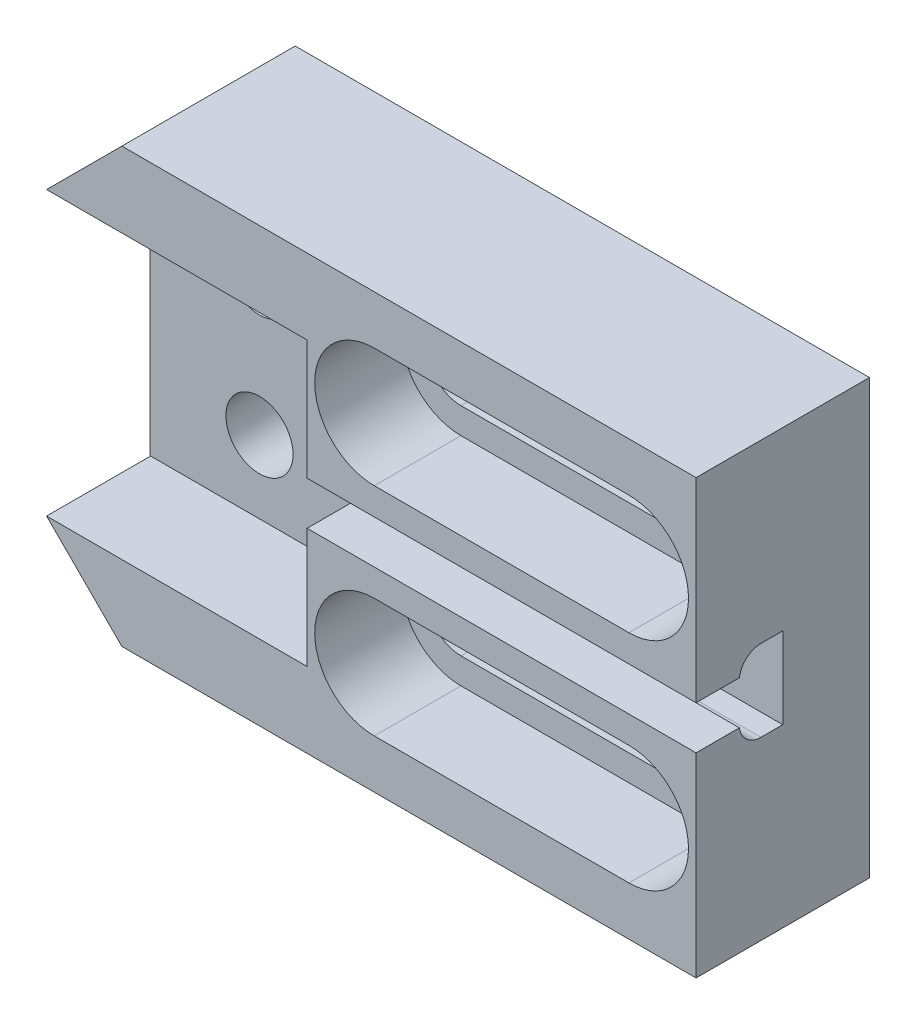
SolidWorks part; units mm, degrees
ref_plane "Front Plane" through (0, 0, 0) normal (0, 0, 1) x (1, 0, 0)
ref_plane "Top Plane" through (0, 0, 0) normal (0, 1, 0) x (1, 0, 0)
ref_plane "Right Plane" through (0, 0, 0) normal (1, 0, 0) x (0, 0, -1)
sketch "ProfileSketch3" plane through (0, 0, 0) normal (0, 0, 1) x (1, 0, 0)
  line L0 (0, 20) -> (30, 20)
  line L1 (0, 0) -> (30, 0)
  line L2 (0, 0) -> (0, 20)
  line L4 (30, 0) -> (30, 20)
  line L9 (15.15, 15) -> (26.9, 15) construction
  line L10 (15.15, 16.55) -> (26.9, 16.55)
  line L11 (15.15, 13.45) -> (26.9, 13.45)
  line L12 (15.15, 5) -> (26.9, 5) construction
  line L13 (15.15, 6.55) -> (26.9, 6.55)
  line L14 (15.15, 3.45) -> (26.9, 3.45)
  arc A4 (15.15, 16.55) -> (15.15, 13.45) centre (15.15, 15) ccw
  arc A5 (26.9, 13.45) -> (26.9, 16.55) centre (26.9, 15) ccw
  arc A6 (15.15, 6.55) -> (15.15, 3.45) centre (15.15, 5) ccw
  arc A7 (26.9, 3.45) -> (26.9, 6.55) centre (26.9, 5) ccw
  point P4 (21.025, 15)
  point P12 (21.025, 5)
  dimension "D4" = 3.1
  dimension "D2" = 3.1
  dimension "D6" = 30
  dimension "D1" = 20
  dimension "D3" = 10
  dimension "D5" = 5
  dimension "D7" = 15.15
extrude "ProfileBoss-Extrude1" add sketch "ProfileSketch3" along normal blind 8
sketch "MicroSwitchCutSketch4" plane through (0, 0, 8) normal (0, 0, 1) x (1, 0, 0)
  line L0 (30, 20) -> (0, 20) construction
  line L1 (0, 16.525) -> (12.05, 16.525)
  line L2 (0, 16.525) -> (0, 3.475)
  line L3 (0, 3.475) -> (12.05, 3.475)
  line L4 (12.05, 16.525) -> (12.05, 3.475)
  dimension "D1" = 12.05
  dimension "D2" = 13.05
  dimension "D3" = 3.475
extrude "MicroSwitchCut-Extrude1" cut sketch "MicroSwitchCutSketch4" against normal blind 4.8
sketch "Sketch5" plane through (0, 0, 3.2) normal (0, 0, 1) x (1, 0, 0)
  line L0 (0, 3.475) -> (12.05, 3.475) construction
  line L2 (12.05, 3.475) -> (12.05, 16.525) construction
  line L4 (12.05, 16.525) -> (0, 16.525) construction
  circle A0 centre (5.05, 13.175) radius 1.55
  circle A1 centre (5.05, 6.825) radius 1.55
  point P10 (11.05, 8.8)
  point P11 (0, 8.8)
  point P12 (15, 21.85)
  point P13 (11.05, 21.85)
  point P14 (15, 0)
  point P15 (15, 21.85)
  point P16 (0, 0)
  point P17 (15, 0)
  point P18 (0, 8.8)
  point P19 (0, 0)
  point P20 (-1, 8.8)
  point P21 (0, 8.8)
  point P22 (-1, 21.85)
  point P23 (-1, 8.8)
  point P24 (15, 21.85)
  point P25 (-1, 21.85)
  point P26 (15, 0)
  point P27 (15, 21.85)
  point P28 (0, 0)
  point P29 (15, 0)
  point P30 (0, 8.8)
  point P31 (0, 0)
  point P32 (11.05, 21.85)
  point P33 (-1, 21.85)
  point P34 (11.05, 8.8)
  point P35 (11.05, 21.85)
  point P36 (-1, 8.8)
  point P37 (0, 8.8)
  point P38 (0, 8.8)
  point P39 (11.05, 8.8)
  point P40 (-1, 21.85)
  point P41 (-1, 8.8)
  point P42 (11.05, 8.8)
  point P43 (11.05, 21.85)
  point P44 (0, 0)
  point P45 (15, 0)
  point P46 (0, 0)
  point P47 (0, 8.8)
  point P48 (-1, 21.85)
  point P49 (15, 21.85)
  point P50 (15, 0)
  point P51 (15, 21.85)
  point P52 (-1, 21.85)
  point P53 (-1, 8.8)
  point P54 (-1, 8.8)
  point P55 (0, 8.8)
  point P56 (-1, 21.85)
  point P57 (-1, 8.8)
  point P58 (-1, 21.85)
  point P59 (11.05, 21.85)
  point P60 (-1, 21.85)
  point P61 (-1, 8.8)
  point P62 (-1, 8.8)
  point P63 (11.05, 8.8)
  point P64 (11.05, 21.85)
  point P65 (11.05, 8.8)
  point P66 (2.75, 0)
  point P67 (-2.75, 0)
  point P68 (0, -2.75)
  point P69 (0, 2.75)
  dimension "D4" = 3.1
  dimension "D3" = 7
  dimension "D2" = 3.35
  dimension "D1" = 3.35
extrude "MicroSwitchMountingHolesCut-Extrude2" cut sketch "Sketch5" against normal blind 3.1
sketch "SmallChannelCableSketch6" plane through (0, 0, 8) normal (0, 0, 1) x (1, 0, 0)
  line L0 (12.05, 3.475) -> (12.05, 16.525) construction
  line L1 (12.05, 11) -> (30, 11)
  line L2 (12.05, 11) -> (12.05, 9)
  line L3 (12.05, 9) -> (30, 9)
  line L4 (30, 11) -> (30, 9)
  line L5 (30, 0) -> (30, 20) construction
  line L6 (0, 3.475) -> (12.05, 3.475) construction
  point P10 (1, 21.85)
  point P11 (1, 13.05)
  point P12 (16, 21.85)
  point P13 (1, 21.85)
  point P14 (16, 0)
  point P15 (16, 21.85)
  point P16 (12.05, 0)
  point P17 (16, 0)
  point P18 (1, 13.05)
  point P19 (0, 13.05)
  point P20 (1, 21.85)
  point P21 (1, 13.05)
  point P22 (16, 21.85)
  point P23 (1, 21.85)
  point P24 (16, 0)
  point P25 (16, 21.85)
  point P26 (0, 0)
  point P27 (16, 0)
  point P28 (0, 13.05)
  point P29 (0, 0)
  point P30 (12.05, 13.05)
  point P31 (1, 13.05)
  point P32 (1, 13.05)
  point P33 (0, 13.05)
  point P34 (12.05, 0)
  point P35 (12.05, 13.05)
  point P36 (0, 0)
  point P37 (12.05, 0)
  point P38 (0, 13.05)
  point P39 (0, 0)
  point P40 (12.05, 13.05)
  point P41 (1, 13.05)
  point P42 (12.05, 0)
  point P43 (12.05, 13.05)
  point P44 (5.05, 9.7)
  point P45 (6.5323, 10.1532)
  point P46 (5.05, 3.35)
  point P47 (6.5323, 3.8032)
  point P48 (5.05, 9.7)
  point P49 (6.5323, 10.1532)
  point P50 (5.05, 3.35)
  point P51 (6.5323, 3.8032)
  point P52 (0, 0)
  point P53 (16, 0)
  point P54 (0, 0)
  point P55 (0, 13.05)
  point P56 (1, 21.85)
  point P57 (16, 21.85)
  point P58 (16, 0)
  point P59 (16, 21.85)
  point P60 (1, 21.85)
  point P61 (1, 13.05)
  point P62 (1, 13.05)
  point P63 (0, 13.05)
  dimension "D2" = 5.525
extrude "SmallChannelCableCut-Extrude3" cut sketch "SmallChannelCableSketch6" against normal blind 2
sketch "LargeChannelCableSketch7" plane through (0, 0, 6) normal (0, 0, 1) x (1, 0, 0)
  line L0 (12.05, 11) -> (12.05, 16.525) construction
  line L1 (12.05, 11.875) -> (30, 11.875)
  line L2 (12.05, 11.875) -> (12.05, 8.125)
  line L3 (12.05, 8.125) -> (30, 8.125)
  line L4 (30, 11.875) -> (30, 8.125)
  line L5 (30, 0) -> (30, 9) construction
  line L6 (30, 11) -> (12.05, 11) construction
  dimension "D1" = 0.875
  dimension "D2" = 3.75
extrude "LargeChannelCableCut-Extrude4" cut sketch "LargeChannelCableSketch7" against normal blind 2
chamfer "Chamfer1" distance 1 angle 45 1 edges at (12.05, 10, 4)
sketch "Sketch6" plane through (0, 0, 8) normal (0, 0, 1) x (1, 0, 0)
  line L0 (15.15, 15) -> (26.9, 15) construction
  line L1 (15.15, 17.75) -> (26.9, 17.75)
  line L2 (15.15, 12.25) -> (26.9, 12.25)
  line L3 (15.15, 5) -> (26.9, 5) construction
  line L4 (15.15, 7.75) -> (26.9, 7.75)
  line L5 (15.15, 2.25) -> (26.9, 2.25)
  arc A0 (15.15, 17.75) -> (15.15, 12.25) centre (15.15, 15) ccw
  arc A1 (26.9, 12.25) -> (26.9, 17.75) centre (26.9, 15) ccw
  arc A2 (15.15, 7.75) -> (15.15, 2.25) centre (15.15, 5) ccw
  arc A3 (26.9, 2.25) -> (26.9, 7.75) centre (26.9, 5) ccw
  point P4 (21.025, 15)
  point P9 (21.025, 5)
  dimension "D1" = 5.5
extrude "MountSLotBoreCut-Extrude1" cut sketch "Sketch6" against normal blind 4
chamfer "Chamfer2" distance 3.5 angle 45 2 edges at (0, 20, 4) (0, 0, 4)
fillet "Fillet3" radius 1 2 edges at (21.025, 11.875, 6) (21.025, 8.125, 6)
equation "\"SK8RodShaftSupportHeight\"= 42mm"
equation "\"SK8RodShaftSupportLength\"= 15mm"
equation "\"SK8MountHoleDiameter\"= 5mm"
equation "\"SK8RiserWidth\"= 6.75mm'Measured to meet Nema17 Mount Hole Center axis"
equation "\"SK8MountHoleFromSide\"= \"SK8RodShaftSupportLength\" / 2"
equation "\"SK8MountHoleFromEitherEnd\"= 5.5mm"
equation "\"MicroSwitchCutOutLength\"= 13.05mm"
equation "\"MicroSwitchHeight\"= 6.55mm"
equation "\"MicroSwitchMountingHoleOffsetFromSide\"= 3.35mm"
equation "\"MicroSwitchTerminalHeight\"= 3.5mm"
equation "\"MicroSwitchExtraMountingHeight\"= 2mm"
equation "\"MicroSwitchDepth\"= 2.8mm"
equation "\"MicroSwitchMountingHoleOffsetFromBottom\"= 7mm"
equation "\"M2HeatInsertHoleDiameter\"= 3mm + .1mm'Add .1mm for printing"
equation "\"M2HeatInsertHoleDepth\"= 3.1mm'Spec"
equation "\"D1@ProfileBoss-Extrude1\" = \"SK8RiserWidth\""
equation "\"D1@MicroSwitchCutSketch4\"=\"MicroSwitchCutOutHeight\""
equation "\"D2@MicroSwitchCutSketch4\" = \"MicroSwitchCutOutLength\""
equation "\"D1@MicroSwitchCut-Extrude1\"=\"MicroSwitchDepth\" + 2mm"
equation "\"D3@Sketch5\"=\"MicroSwitchMountingHoleOffsetFromBottom\""
equation "\"D4@Sketch5\"=\"M2HeatInsertHoleDiameter\""
equation "\"D1@MicroSwitchMountingHolesCut-Extrude2\" = \"M2HeatInsertHoleDepth\""
equation "\"MicroSwitchCutOutHeight\"= \"MicroSwitchExtraMountingHeight\" + \"MicroSwitchTerminalHeight\" + \"MicroSwitchHeight\""
equation "\"EndStopCableWidth\"= 3.75mm"
equation "\"D1@SmallChannelCableSketch6\" = \"EndStopCableDepth\""
equation "\"EndStopCableDepth\"= 2mm"
equation "\"D1@SmallChannelCableCut-Extrude3\"=\"EndStopCableDepth\""
equation "\"D1@LargeChannelCableSketch7\" =  ( \"EndStopCableWidth\" - \"EndStopCableDepth\" )  / 2"
equation "\"D2@LargeChannelCableSketch7\" = \"EndStopCableWidth\""
equation "\"D1@LargeChannelCableCut-Extrude4\" = \"EndStopCableDepth\""
equation "\"D6@ProfileSketch3\"=\"SK8RodShaftSupportLength\"  *2"
equation "\"D2@Sketch5\"=\"MicroSwitchMountingHoleOffsetFromSide\""
equation "\"D1@Sketch6\"= \"SK8MountHoleFromEitherEnd\""
equation "\"D1@ProfileSketch3\"=\"YAxisEndStopMicroSwitchHolderHeight\""
equation "\"Nema17StepperMountSlotDistance\"=31"
equation "\"YAxisEndStopMicroSwitchHolderHeight\"= \"YAxisEndStopHolderDistanceBetweenMountingScrews\" * 2"
equation "\"M3ScrewDiameter\"= 3mm + .1mm'Add .1mm for printing"
equation "\"D3@MicroSwitchCutSketch4\"=(\"YAxisEndStopMicroSwitchHolderHeight\"-\"MicroSwitchCutOutLength\")/2"
equation "\"D2@SmallChannelCableSketch6\"=(\"MicroSwitchCutOutLength\"-\"EndStopCableDepth\")/2"
equation "\"D2@ProfileSketch3\"=\"M3ScrewDiameter\""
equation "\"D4@ProfileSketch3\"=\"M3ScrewDiameter\""
equation "\"D5@ProfileSketch3\"=\"YAxisEndStopHolderDistanceBetweenMountingScrews\"/2"
equation "\"D7@ProfileSketch3\"=\"MicroSwitchCutOutHeight\" + \"M3ScrewDiameter\""
equation "\"YAxisEndStopHolderDistanceBetweenMountingScrews\"= 10mm"
equation "\"D3@ProfileSketch3\"=\"YAxisEndStopHolderDistanceBetweenMountingScrews\""
equation "\"D1@Sketch5\"=\"MicroSwitchMountingHoleOffsetFromSide\""
equation "\"YAxisEndStopMicroSwitchHolderThickness\"= 8mm"
